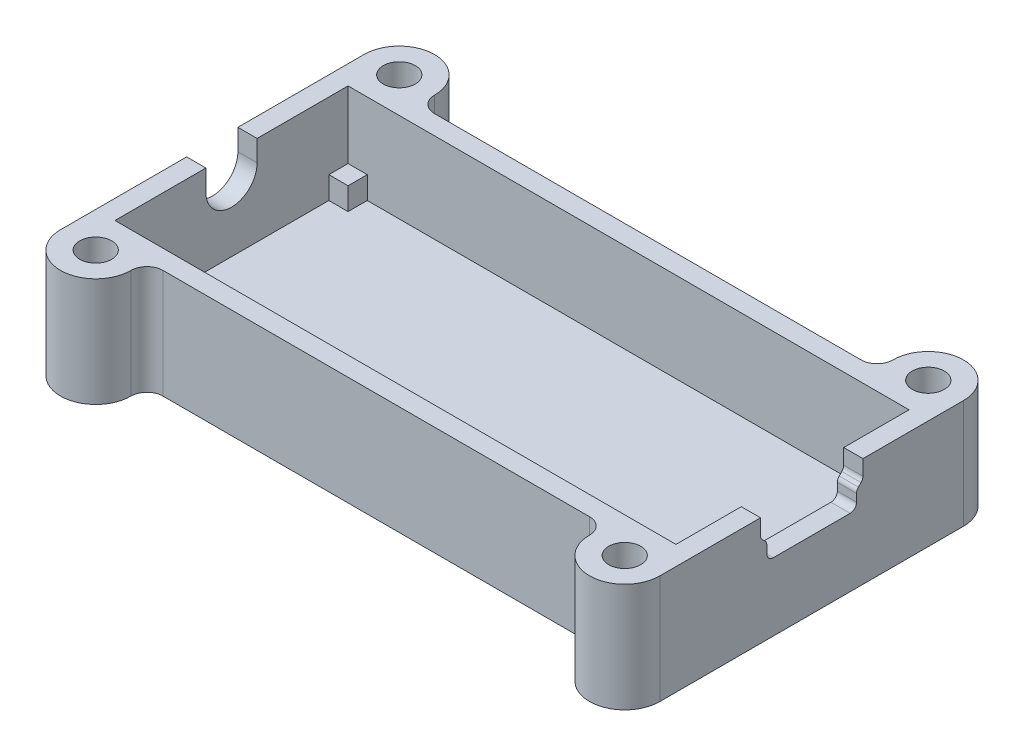
SolidWorks part; units mm, degrees
ref_plane "Front Plane" through (0, 0, 0) normal (0, 0, 1) x (1, 0, 0)
ref_plane "Top Plane" through (0, 0, 0) normal (0, 1, 0) x (1, 0, 0)
ref_plane "Right Plane" through (0, 0, 0) normal (1, 0, 0) x (0, 0, -1)
sketch "Sketch1" plane through (0, 0, 0) normal (0, 1, 0) x (1, 0, 0)
  line L0 (-21.9, 9.1) -> (-23.4, 9.1) construction
  line L1 (-21.9, 9.1) -> (21.9, 9.1)
  line L2 (-21.9, 9.1) -> (-21.9, -9.1)
  line L3 (-21.9, -9.1) -> (21.9, -9.1)
  line L4 (21.9, 9.1) -> (21.9, -9.1)
  line L5 (-21.9, 9.1) -> (21.9, -9.1) construction
  line L6 (-21.9, -9.1) -> (21.9, 9.1) construction
  line L7 (23.4, -10.6) -> (-23.4, -10.6)
  line L8 (23.4, -10.6) -> (23.4, 10.6)
  line L9 (23.4, 10.6) -> (-23.4, 10.6)
  line L10 (-23.4, -10.6) -> (-23.4, 10.6)
  line L11 (23.4, -10.6) -> (-23.4, 10.6) construction
  line L12 (23.4, 10.6) -> (-23.4, -10.6) construction
  line L13 (-21.9, 9.1) -> (-21.9, 10.6) construction
  line L14 (-19.4, 11.85) -> (-17.9, 11.85) construction
  line L15 (-23.4, 11.85) -> (-23.4, 10.6)
  line L16 (0, 30.5142) -> (0, -27.0472) construction
  line L17 (-40.1948, 0) -> (31.8876, 0) construction
  line L18 (-17.9, 11.85) -> (-17.9, 10.6)
  line L19 (17.9, 11.85) -> (17.9, 10.6)
  line L20 (23.4, 11.85) -> (23.4, 10.6)
  line L21 (23.4, -11.85) -> (23.4, -10.6)
  line L22 (17.9, -11.85) -> (17.9, -10.6)
  line L23 (-17.9, -11.85) -> (-17.9, -10.6)
  line L24 (-23.4, -11.85) -> (-23.4, -10.6)
  circle A0 centre (-20.65, 11.85) radius 1.25
  circle A1 centre (-20.65, 11.85) radius 2.75
  circle A2 centre (20.65, 11.85) radius 1.25
  circle A3 centre (20.65, 11.85) radius 2.75
  circle A4 centre (20.65, -11.85) radius 1.25
  circle A5 centre (20.65, -11.85) radius 2.75
  circle A6 centre (-20.65, -11.85) radius 1.25
  circle A7 centre (-20.65, -11.85) radius 2.75
  point P0 (0, 0)
  point P6 (0, 0)
  dimension "D4" = 2.5
  dimension "D1" = 18.2
  dimension "D2" = 43.8
  dimension "D3" = 1.5
extrude "Boss-Extrude1" add sketch "Sketch1" along normal blind 7 contours A1 L9 L18 | L9 A1 A0 | A1 L15 L9 | L9 A3 L19 | A3 L9 A2 | L20 A3 L9 | A5 L7 L22 | A5 L7 A4 | A5 L21 L7 | L24 A7 L7 | A7 L7 A6 | L7 A7 L23 | L7 A7 L3 L2 L1 A1 L9 L10 | A7 L7 | L3 A7 L7 A5 | L7 A5 | A5 L7 L8 L9 A3 L1 L4 L3 | A3 L9 | L1 A3 L9 A1 | A1 L9 region at (-22.6592, 0, 0) region at (0, 0, -9.8377) region at (-20.65, 0, -9.9833) region at (22.6592, 0, 0) region at (20.65, 0, -9.9833) region at (-23.2577, 0, -11.2231) region at (-23.3108, 0, -10.909) region at (-17.9892, 0, -10.909) region at (0, 0, 9.8377) region at (-20.65, 0, 9.9833) region at (18.0423, 0, -11.2231) region at (17.9892, 0, -10.909) region at (23.3108, 0, -10.909) region at (20.65, 0, 9.9833) region at (-18.0423, 0, 11.2231) region at (-17.9892, 0, 10.909) region at (-23.3108, 0, 10.909) region at (23.2577, 0, 11.2231) region at (23.3108, 0, 10.909) region at (17.9892, 0, 10.909)
sketch "Sketch3" plane through (0, 0, 0) normal (0, -1, 0) x (1, 0, 0)
  line L8 (-23.4, 11.85) -> (-23.4, -11.85)
  line L9 (-17.9, -11.85) -> (-17.9, -10.6)
  line L10 (-17.9, -10.6) -> (17.9, -10.6)
  line L11 (17.9, -10.6) -> (17.9, -11.85)
  line L12 (23.4, -11.85) -> (23.4, 11.85)
  line L13 (17.9, 11.85) -> (17.9, 10.6)
  line L14 (17.9, 10.6) -> (-17.9, 10.6)
  line L15 (-17.9, 10.6) -> (-17.9, 11.85)
  line L16 (-23.4, 11.85) -> (-23.4, -11.85)
  line L17 (-17.9, -11.85) -> (-17.9, -10.6)
  line L18 (-17.9, -10.6) -> (17.9, -10.6)
  line L19 (17.9, -10.6) -> (17.9, -11.85)
  line L20 (23.4, -11.85) -> (23.4, 11.85)
  line L21 (17.9, 11.85) -> (17.9, 10.6)
  line L22 (17.9, 10.6) -> (-17.9, 10.6)
  line L23 (-17.9, 10.6) -> (-17.9, 11.85)
  circle A0 centre (-20.65, -11.85) radius 1.25 construction
  circle A1 centre (20.65, -11.85) radius 1.25 construction
  circle A2 centre (20.65, 11.85) radius 1.25 construction
  circle A3 centre (-20.65, 11.85) radius 1.25 construction
  arc A4 (-17.9, 11.85) -> (-23.4, 11.85) centre (-20.65, 11.85) ccw
  arc A5 (-23.4, -11.85) -> (-17.9, -11.85) centre (-20.65, -11.85) ccw
  arc A6 (17.9, -11.85) -> (23.4, -11.85) centre (20.65, -11.85) ccw
  arc A7 (23.4, 11.85) -> (17.9, 11.85) centre (20.65, 11.85) ccw
  arc A8 (-17.9, 11.85) -> (-23.4, 11.85) centre (-20.65, 11.85) ccw
  arc A9 (-23.4, -11.85) -> (-17.9, -11.85) centre (-20.65, -11.85) ccw
  arc A10 (17.9, -11.85) -> (23.4, -11.85) centre (20.65, -11.85) ccw
  arc A11 (23.4, 11.85) -> (17.9, 11.85) centre (20.65, 11.85) ccw
  circle A12 centre (-20.65, -11.85) radius 1.25
  circle A13 centre (20.65, -11.85) radius 1.25
  circle A14 centre (20.65, 11.85) radius 1.25
  circle A15 centre (-20.65, 11.85) radius 1.25
  dimension "D1" = 0
extrude "Boss-Extrude2" add sketch "Sketch3" along normal blind 1.5
sketch "Sketch4" plane through (-23.4, 0, 0) normal (-1, 0, 0) x (0, 0, 1)
  line L0 (-9.1, 0) -> (9.1, 0) construction
  line L1 (-9.1, 0) -> (9.1, 0)
  line L2 (0, 7) -> (0, -1.5) construction
  line L3 (11.85, 7) -> (-11.85, 7) construction
  line L4 (11.85, -1.5) -> (-11.85, -1.5) construction
  line L5 (0, 3.35) -> (11.85, 3.35) construction
  line L6 (11.85, 7) -> (11.85, -1.5) construction
  line L7 (-2, 5.35) -> (-2, 7)
  line L8 (2, 5.35) -> (2, 7)
  line L9 (-2, 7) -> (2, 7)
  circle A0 centre (0, 5.35) radius 2
  line M6 (11.85, 7) -> (-11.85, 7)
  dimension "D2" = 4
  dimension "D1" = 3.35
extrude "Cut-Extrude1" cut sketch "Sketch4" against normal up to next contours A0 L9 | A0 L7 M6 | A0 L8 M6 region at (-23.4, 5.27, 0) region at (-23.4, 6.6076, -1.7528) region at (-23.4, 6.6076, 1.7528)
sketch "Sketch5" plane through (0, 0, 0) normal (0, 1, 0) x (1, 0, 0)
  line L0 (0, 18.1559) -> (0, -18.574) construction
  line L1 (-21.9, 9.1) -> (-20.4, 9.1)
  line L2 (-21.9, 9.1) -> (-21.9, 7.6)
  line L3 (-21.9, 7.6) -> (-20.4, 7.6)
  line L4 (-20.4, 9.1) -> (-20.4, 7.6)
  line L5 (-28.7323, 0) -> (29.8474, 0) construction
  line L6 (21.9, 9.1) -> (21.9, 7.6)
  line L7 (21.9, 9.1) -> (20.4, 9.1)
  line L8 (20.4, 9.1) -> (20.4, 7.6)
  line L9 (21.9, 7.6) -> (20.4, 7.6)
  line L10 (-21.9, -9.1) -> (-21.9, -7.6)
  line L11 (-21.9, -9.1) -> (-20.4, -9.1)
  line L12 (-20.4, -9.1) -> (-20.4, -7.6)
  line L13 (-21.9, -7.6) -> (-20.4, -7.6)
  line L14 (21.9, -9.1) -> (21.9, -7.6)
  line L15 (21.9, -9.1) -> (20.4, -9.1)
  line L16 (20.4, -9.1) -> (20.4, -7.6)
  line L17 (21.9, -7.6) -> (20.4, -7.6)
  dimension "D1" = 1.5
extrude "Boss-Extrude3" add sketch "Sketch5" along normal blind 1.75
sketch "Sketch6" plane through (23.4, 0, 0) normal (1, 0, 0) x (0, 0, -1)
  line L1 (0, 7) -> (0, -1.5) construction
  line L2 (11.85, 7) -> (-11.85, 7) construction
  line L3 (11.85, -1.5) -> (-11.85, -1.5) construction
  line L4 (7.6, 0) -> (-7.6, 0) construction
  line L5 (7.6, 0) -> (-7.6, 0)
  line L6 (-4, 5.1) -> (4, 5.1) construction
  line L7 (-4, 7) -> (4, 7)
  line L8 (-4, 7) -> (-4, 3.8)
  line L9 (-4, 3.8) -> (4, 3.8)
  line L10 (4, 7) -> (4, 3.8)
  line L11 (-4, 7) -> (4, 3.8) construction
  line L12 (-4, 3.8) -> (4, 7) construction
  line L13 (-3.5, 5.1) -> (-3.5, 3.8)
  line L14 (-3.5, 5.1) -> (-4, 5.6)
  line L15 (3.5, 5.1) -> (3.5, 3.8)
  line L16 (3.5, 5.1) -> (4, 5.6)
  point P8 (0, 5.4)
  line M9 (11.85, 7) -> (-11.85, 7)
  dimension "D1" = 3.8
  dimension "D2" = 8
  dimension "D3" = 1.3
  dimension "D4" = 7
  dimension "D5" = 45
extrude "Cut-Extrude2" cut sketch "Sketch6" against normal up to next contours L10 L8 L9 M9 region at (23.4, 5.4527, 0)
fillet "Fillet1" radius 1.25 4 edges at (-17.9, 2.75, 10.6) (17.9, 2.75, 10.6) (17.9, 2.75, -10.6) (-17.9, 2.75, -10.6)
fillet "Fillet2" radius 0.5 6 edges at (22.65, 3.8, 3.5) (22.65, 3.8, -3.5) (22.65, 5.1, -3.5) (22.65, 5.6, -4) (22.65, 5.1, 3.5) (22.65, 5.6, 4)
